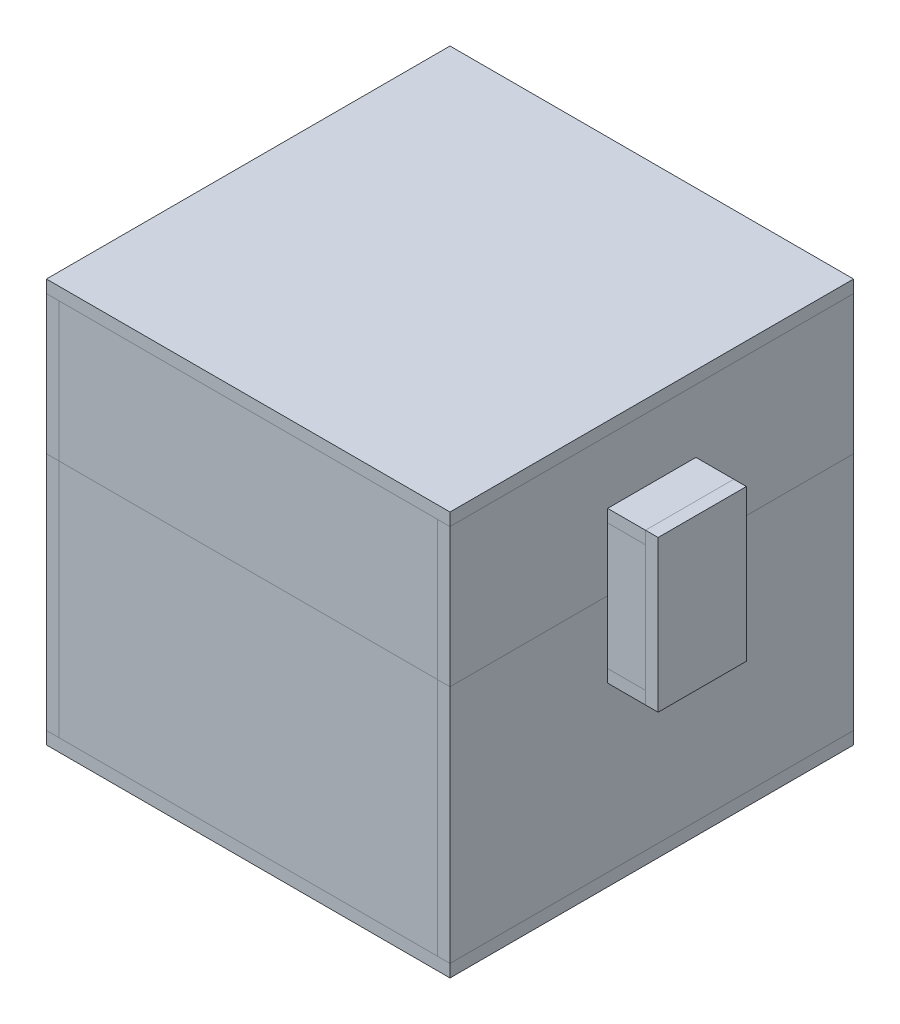
SolidWorks part; units mm, degrees
ref_plane "Front Plane" through (0, 0, 0) normal (0, 0, 1) x (1, 0, 0)
ref_plane "Top Plane" through (0, 0, 0) normal (0, 1, 0) x (1, 0, 0)
ref_plane "Right Plane" through (0, 0, 0) normal (1, 0, 0) x (0, 0, -1)
sketch "Sketch1" plane through (0, 0, 0) normal (0, 1, 0) x (1, 0, 0)
  line L1 (-101.6, -101.6) -> (101.6, -101.6)
  line L2 (-101.6, -101.6) -> (-101.6, 101.6)
  line L3 (-101.6, 101.6) -> (101.6, 101.6)
  line L4 (101.6, -101.6) -> (101.6, 101.6)
  line L5 (-101.6, -101.6) -> (101.6, 101.6) construction
  line L6 (-101.6, 101.6) -> (101.6, -101.6) construction
  point P0 (0, 0)
  dimension "D1" = 203.2
extrude "Boss-Extrude1" add sketch "Sketch1" along normal blind 127
sketch "Sketch2" plane through (0, 127, 0) normal (0, 1, 0) x (1, 0, 0)
  line L20 (95.25, -95.25) -> (95.25, 95.25)
  line L21 (95.25, 95.25) -> (-95.25, 95.25)
  line L22 (-95.25, 95.25) -> (-95.25, -95.25)
  line L23 (-95.25, -95.25) -> (95.25, -95.25)
  line L24 (95.25, -95.25) -> (95.25, 95.25)
  line L25 (95.25, 95.25) -> (-95.25, 95.25)
  line L26 (-95.25, 95.25) -> (-95.25, -95.25)
  line L27 (-95.25, -95.25) -> (95.25, -95.25)
  dimension "D1" = 6.35
extrude "Cut-Extrude1" cut sketch "Sketch2" against normal blind 120.65
sketch "Sketch3" plane through (0, 127, 0) normal (0, 1, 0) x (1, 0, 0)
  line L0 (-101.6, -101.6) -> (101.6, -101.6) construction
  line L1 (101.6, -101.6) -> (101.6, 101.6) construction
  line L2 (-101.6, 101.6) -> (-101.6, -101.6) construction
  line L3 (101.6, 101.6) -> (-101.6, 101.6) construction
  line L4 (-101.6, -101.6) -> (101.6, -101.6)
  line L5 (101.6, -101.6) -> (101.6, 101.6)
  line L6 (-101.6, 101.6) -> (-101.6, -101.6)
  line L7 (101.6, 101.6) -> (-101.6, 101.6)
extrude "Boss-Extrude2" add sketch "Sketch3" along normal blind 76.2 separate body
ref_plane "Plane1" through (-101.6, 127, 101.6) normal (1, 0, 0) x (0, 0, -1)
sketch "Sketch5" plane through (0, 203.2, 0) normal (0, 1, 0) x (1, 0, 0)
  line L8 (-95.25, 95.25) -> (-95.25, -95.25)
  line L9 (-95.25, -95.25) -> (95.25, -95.25)
  line L10 (95.25, -95.25) -> (95.25, 95.25)
  line L11 (95.25, 95.25) -> (-95.25, 95.25)
  line L12 (-95.25, 95.25) -> (-95.25, -95.25)
  line L13 (-95.25, -95.25) -> (95.25, -95.25)
  line L14 (95.25, -95.25) -> (95.25, 95.25)
  line L15 (95.25, 95.25) -> (-95.25, 95.25)
  dimension "D1" = 6.35
extrude "Cut-Extrude2" cut sketch "Sketch5" against normal blind 69.85 from offset 6.35 offset against normal yes
sketch "Sketch6" plane through (0, 0, 0) normal (1, 0, 0) x (0, 0, -1)
  line L0 (-101.6, 127) -> (101.6, 127) construction
  line L1 (-22.225, 88.9) -> (22.225, 88.9)
  line L2 (-22.225, 88.9) -> (-22.225, 165.1)
  line L3 (-22.225, 165.1) -> (22.225, 165.1)
  line L4 (22.225, 88.9) -> (22.225, 165.1)
  line L5 (-22.225, 88.9) -> (22.225, 165.1) construction
  line L6 (-22.225, 165.1) -> (22.225, 88.9) construction
  point P0 (0, 127)
  dimension "D1" = 44.45
  dimension "D2" = 76.2
extrude "Boss-Extrude3" add sketch "Sketch6" along normal blind 25.4 from surface separate body starting at face at (101.6, 165.1, 0)
sketch "Sketch7" plane through (-101.6, 0, 0) normal (-1, 0, 0) x (0, 0, 1)
  line L0 (-76.2, 140) -> (-49.7, 140) construction
  line L1 (-101.6, 127) -> (101.6, 127) construction
  line L2 (-101.6, 203.2) -> (-101.6, 127) construction
  line L3 (0, -111.76) -> (0, 111.76) construction
  circle A0 centre (-76.2, 140) radius 2.5
  circle A1 centre (-49.7, 140) radius 2.5
  circle A2 centre (49.7, 140) radius 2.5
  circle A3 centre (76.2, 140) radius 2.5
  dimension "D2" = 5
  dimension "D1" = 26.5
  dimension "D3" = 13
  dimension "D4" = 25.4
extrude "Cut-Extrude3" cut sketch "Sketch7" against normal up to next (6.35 mm away)
mirror "Mirror4" about plane through (0, 127, 0) normal (0, -1, 0) of "Cut-Extrude3"
sketch "Sketch9" plane through (101.6, 0, 0) normal (-1, 0, 0) x (0, 0, 1)
  line L8 (-15.875, 158.75) -> (-15.875, 95.25)
  line L9 (-15.875, 95.25) -> (15.875, 95.25)
  line L10 (15.875, 95.25) -> (15.875, 158.75)
  line L11 (15.875, 158.75) -> (-15.875, 158.75)
  line L12 (-15.875, 158.75) -> (-15.875, 95.25)
  line L13 (-15.875, 95.25) -> (15.875, 95.25)
  line L14 (15.875, 95.25) -> (15.875, 158.75)
  line L15 (15.875, 158.75) -> (-15.875, 158.75)
  dimension "D1" = 6.35
extrude "Cut-Extrude4" cut sketch "Sketch9" against normal blind 19.05 contours L12 L13 L14 L15
sketch "Sketch10" plane through (120.65, 0, 0) normal (-1, 0, 0) x (0, 0, 1)
  line L4 (15.875, 158.75) -> (-15.875, 158.75)
  line L5 (-15.875, 158.75) -> (-15.875, 95.25)
  line L6 (-15.875, 95.25) -> (15.875, 95.25)
  line L7 (15.875, 95.25) -> (15.875, 158.75)
  line L8 (15.875, 158.75) -> (-15.875, 158.75)
  line L9 (-15.875, 158.75) -> (-15.875, 95.25)
  line L10 (-15.875, 95.25) -> (15.875, 95.25)
  line L11 (15.875, 95.25) -> (15.875, 158.75)
  dimension "D1" = 0
extrude "Boss-Extrude4" add sketch "Sketch10" along normal blind 19.05 separate body
sketch "Sketch12" plane through (101.6, 0, 0) normal (-1, 0, 0) x (0, 0, 1)
  line L0 (0, -111.76) -> (0, 111.76) construction
  line L1 (-9.5, 101.6) -> (9.5, 101.6)
  line L2 (-9.5, 101.6) -> (-9.5, 120.6)
  line L3 (-9.5, 120.6) -> (9.5, 120.6)
  line L4 (9.5, 101.6) -> (9.5, 120.6)
  line L5 (-9.5, 101.6) -> (9.5, 120.6) construction
  line L6 (-9.5, 120.6) -> (9.5, 101.6) construction
  line L7 (-15.875, 95.25) -> (15.875, 95.25) construction
  point P0 (0, 111.1)
  dimension "D1" = 19
  dimension "D2" = 6.35
extrude "Cut-Extrude5" cut sketch "Sketch12" against normal blind 4
sketch "Sketch13" plane through (105.6, 0, 0) normal (-1, 0, 0) x (0, 0, 1)
  line L0 (0, -111.76) -> (0, 111.76) construction
  line L1 (9.5, 101.6) -> (9.5, 120.6) construction
  circle A0 centre (0, 111.1) radius 4.25
  point P4 (0, 0)
  point P7 (9.5, 111.1)
  dimension "D1" = 8.5
extrude "Cut-Extrude6" cut sketch "Sketch13" against normal blind 3 contours A0
sketch "Sketch15" plane through (127, 0, 0) normal (1, 0, 0) x (0, 0, -1)
  line L4 (22.225, 88.9) -> (22.225, 165.1)
  line L5 (22.225, 165.1) -> (-22.225, 165.1)
  line L6 (-22.225, 165.1) -> (-22.225, 88.9)
  line L7 (-22.225, 88.9) -> (22.225, 88.9)
  line L8 (22.225, 88.9) -> (22.225, 165.1)
  line L9 (22.225, 165.1) -> (-22.225, 165.1)
  line L10 (-22.225, 165.1) -> (-22.225, 88.9)
  line L11 (-22.225, 88.9) -> (22.225, 88.9)
  dimension "D1" = 0
extrude "Boss-Extrude5" add sketch "Sketch15" against normal blind 6.35 separate body contours L8 L9 L10 L11
sketch "Sketch16" plane through (0, 165.1, 0) normal (0, 1, 0) x (1, 0, 0)
  line L0 (120.65, 22.225) -> (120.65, -22.225) construction
  line L1 (120.65, 22.225) -> (120.65, -22.225)
  line L4 (101.6, 22.225) -> (101.6, -22.225)
  line L5 (101.6, -22.225) -> (127, -22.225)
  line L6 (127, -22.225) -> (127, 22.225)
  line L7 (127, 22.225) -> (101.6, 22.225)
  line L8 (101.6, 22.225) -> (101.6, -22.225)
  line L9 (101.6, -22.225) -> (120.65, -22.225)
  line L11 (120.65, 22.225) -> (101.6, 22.225)
  dimension "D1" = 0
extrude "Boss-Extrude7" add sketch "Sketch16" against normal blind 6.35 separate body contours L8 L9 L1 L11
sketch "Sketch18" plane through (0, 88.9, 0) normal (0, -1, 0) x (1, 0, 0)
  line L4 (101.6, -22.225) -> (120.65, -22.225)
  line L5 (101.6, 22.225) -> (101.6, -22.225)
  line L6 (120.65, 22.225) -> (101.6, 22.225)
  line L7 (120.65, -22.225) -> (120.65, 22.225)
  line L8 (101.6, -22.225) -> (120.65, -22.225)
  line L9 (101.6, 22.225) -> (101.6, -22.225)
  line L10 (120.65, 22.225) -> (101.6, 22.225)
  line L11 (120.65, -22.225) -> (120.65, 22.225)
  dimension "D1" = 0
extrude "Boss-Extrude8" add sketch "Sketch18" against normal blind 6.35 separate body contours L8 L11 L10 L9
sketch "Sketch19" plane through (0, 0, 15.875) normal (0, 0, 1) x (1, 0, 0)
  line L4 (120.65, 95.25) -> (120.65, 158.75)
  line L5 (120.65, 158.75) -> (101.6, 158.75)
  line L6 (101.6, 158.75) -> (101.6, 95.25)
  line L7 (101.6, 95.25) -> (120.65, 95.25)
  line L8 (120.65, 95.25) -> (120.65, 158.75)
  line L9 (120.65, 158.75) -> (101.6, 158.75)
  line L10 (101.6, 158.75) -> (101.6, 95.25)
  line L11 (101.6, 95.25) -> (120.65, 95.25)
  dimension "D1" = 0
extrude "Boss-Extrude12" add sketch "Sketch19" along normal blind 6.35 separate body contours L8 L9 L10 L11
sketch "Sketch21" plane through (0, 0, -15.875) normal (0, 0, -1) x (-1, 0, 0)
  line L4 (-120.65, 158.75) -> (-120.65, 95.25)
  line L5 (-120.65, 95.25) -> (-101.6, 95.25)
  line L6 (-101.6, 95.25) -> (-101.6, 158.75)
  line L7 (-101.6, 158.75) -> (-120.65, 158.75)
  line L8 (-120.65, 158.75) -> (-120.65, 95.25)
  line L9 (-120.65, 95.25) -> (-101.6, 95.25)
  line L10 (-101.6, 95.25) -> (-101.6, 158.75)
  line L11 (-101.6, 158.75) -> (-120.65, 158.75)
  dimension "D1" = 0
extrude "Boss-Extrude13" add sketch "Sketch21" along normal blind 6.35 separate body
delete or keep bodies "Body-Delete/Keep 1" type delete bodies bodies 108
sketch "Sketch22" plane through (0, 203.2, 0) normal (0, 1, 0) x (1, 0, 0)
  line L4 (-101.6, 101.6) -> (-101.6, -101.6)
  line L5 (-101.6, -101.6) -> (101.6, -101.6)
  line L6 (101.6, -101.6) -> (101.6, 101.6)
  line L7 (101.6, 101.6) -> (-101.6, 101.6)
  line L8 (-101.6, 101.6) -> (-101.6, -101.6)
  line L9 (-101.6, -101.6) -> (101.6, -101.6)
  line L10 (101.6, -101.6) -> (101.6, 101.6)
  line L11 (101.6, 101.6) -> (-101.6, 101.6)
  dimension "D1" = 0
extrude "Boss-Extrude14" add sketch "Sketch22" against normal blind 6.35 separate body
sketch "Sketch23" plane through (101.6, 0, 0) normal (1, 0, 0) x (0, 0, -1)
  line L0 (101.6, 196.85) -> (-101.6, 196.85)
  line L12 (-101.6, 127) -> (101.6, 127)
  line L13 (101.6, 127) -> (101.6, 203.2)
  line L14 (101.6, 203.2) -> (-101.6, 203.2)
  line L15 (-101.6, 203.2) -> (-101.6, 127)
  line L16 (-101.6, 127) -> (101.6, 127)
  line L17 (101.6, 127) -> (101.6, 196.85)
  line L19 (-101.6, 196.85) -> (-101.6, 127)
  dimension "D1" = 0
extrude "Boss-Extrude16" add sketch "Sketch23" against normal blind 6.35 separate body contours L16 L17 L0 L19
sketch "Sketch24" plane through (-101.6, 0, 0) normal (-1, 0, 0) x (0, 0, 1)
  line L0 (-101.6, 196.85) -> (101.6, 196.85)
  line L4 (-101.6, 127) -> (101.6, 127)
  line L5 (101.6, 127) -> (101.6, 203.2)
  line L6 (101.6, 203.2) -> (-101.6, 203.2)
  line L7 (-101.6, 203.2) -> (-101.6, 127)
  line L8 (-101.6, 127) -> (101.6, 127)
  line L9 (101.6, 127) -> (101.6, 196.85)
  line L11 (-101.6, 196.85) -> (-101.6, 127)
  circle A0 centre (76.2, 140) radius 2.5 construction
  circle A1 centre (49.7, 140) radius 2.5 construction
  circle A2 centre (-49.7, 140) radius 2.5 construction
  circle A3 centre (-76.2, 140) radius 2.5 construction
  circle A4 centre (76.2, 140) radius 2.5
  circle A5 centre (49.7, 140) radius 2.5
  circle A6 centre (-49.7, 140) radius 2.5
  circle A7 centre (-76.2, 140) radius 2.5
  dimension "D1" = 0
extrude "Boss-Extrude17" add sketch "Sketch24" against normal blind 6.35 separate body
sketch "Sketch25" plane through (0, 0, 101.6) normal (0, 0, 1) x (1, 0, 0)
  line L0 (-101.6, 127) -> (101.6, 127) construction
  line L1 (-95.25, 127) -> (-95.25, 196.85) construction
  line L2 (95.25, 196.85) -> (95.25, 127) construction
  line L3 (-101.6, 196.85) -> (101.6, 196.85) construction
  line L4 (-95.25, 127) -> (95.25, 127)
  line L5 (-95.25, 127) -> (-95.25, 196.85)
  line L6 (95.25, 196.85) -> (95.25, 127)
  line L7 (-95.25, 196.85) -> (95.25, 196.85)
extrude "Boss-Extrude18" add sketch "Sketch25" against normal blind 6.35 separate body
sketch "Sketch26" plane through (0, 0, -101.6) normal (0, 0, -1) x (-1, 0, 0)
  line L4 (95.25, 127) -> (95.25, 196.85)
  line L5 (-95.25, 127) -> (95.25, 127)
  line L6 (-95.25, 196.85) -> (-95.25, 127)
  line L7 (95.25, 196.85) -> (-95.25, 196.85)
  line L8 (95.25, 127) -> (95.25, 196.85)
  line L9 (-95.25, 127) -> (95.25, 127)
  line L10 (-95.25, 196.85) -> (-95.25, 127)
  line L11 (95.25, 196.85) -> (-95.25, 196.85)
  dimension "D1" = 0
extrude "Boss-Extrude19" add sketch "Sketch26" against normal blind 6.35 separate body contours L8 L11 L10 L9
delete or keep bodies "Body-Delete/Keep 2" type delete bodies bodies 106
sketch "Sketch27" plane through (0, 0, 0) normal (0, -1, 0) x (1, 0, 0)
  line L4 (101.6, -101.6) -> (101.6, 101.6)
  line L5 (101.6, 101.6) -> (-101.6, 101.6)
  line L6 (-101.6, 101.6) -> (-101.6, -101.6)
  line L7 (-101.6, -101.6) -> (101.6, -101.6)
  line L8 (101.6, -101.6) -> (101.6, 101.6)
  line L9 (101.6, 101.6) -> (-101.6, 101.6)
  line L10 (-101.6, 101.6) -> (-101.6, -101.6)
  line L11 (-101.6, -101.6) -> (101.6, -101.6)
  dimension "D1" = 0
extrude "Boss-Extrude20" add sketch "Sketch27" against normal blind 6.35 separate body
sketch "Sketch28" plane through (101.6, 0, 0) normal (1, 0, 0) x (0, 0, -1)
  line L0 (-101.6, 6.35) -> (101.6, 6.35)
  line L4 (-101.6, 0) -> (101.6, 0)
  line L5 (101.6, 0) -> (101.6, 127)
  line L6 (101.6, 127) -> (-101.6, 127)
  line L7 (-101.6, 127) -> (-101.6, 0)
  line L9 (101.6, 6.35) -> (101.6, 127)
  line L10 (101.6, 127) -> (-101.6, 127)
  line L11 (-101.6, 127) -> (-101.6, 6.35)
  dimension "D1" = 0
extrude "Boss-Extrude21" add sketch "Sketch28" against normal blind 6.35 separate body
sketch "Sketch29" plane through (-101.6, 0, 0) normal (-1, 0, 0) x (0, 0, 1)
  line L4 (101.6, 6.35) -> (101.6, 127)
  line L5 (101.6, 127) -> (-101.6, 127)
  line L6 (-101.6, 127) -> (-101.6, 6.35)
  line L7 (-101.6, 6.35) -> (101.6, 6.35)
  line L8 (101.6, 6.35) -> (101.6, 127)
  line L9 (101.6, 127) -> (-101.6, 127)
  line L10 (-101.6, 127) -> (-101.6, 6.35)
  line L11 (-101.6, 6.35) -> (101.6, 6.35)
  circle A0 centre (76.2, 114) radius 2.5 construction
  circle A1 centre (49.7, 114) radius 2.5 construction
  circle A2 centre (-49.7, 114) radius 2.5 construction
  circle A3 centre (-76.2, 114) radius 2.5 construction
  circle A4 centre (76.2, 114) radius 2.5
  circle A5 centre (49.7, 114) radius 2.5
  circle A6 centre (-49.7, 114) radius 2.5
  circle A7 centre (-76.2, 114) radius 2.5
  dimension "D1" = 0
extrude "Boss-Extrude22" add sketch "Sketch29" against normal blind 6.35 separate body
sketch "Sketch30" plane through (0, 0, 101.6) normal (0, 0, 1) x (1, 0, 0)
  line L0 (101.6, 6.35) -> (-101.6, 6.35) construction
  line L1 (95.25, 127) -> (95.25, 6.35) construction
  line L2 (-95.25, 127) -> (95.25, 127) construction
  line L3 (-95.25, 6.35) -> (-95.25, 127) construction
  line L4 (95.25, 6.35) -> (-95.25, 6.35)
  line L5 (95.25, 127) -> (95.25, 6.35)
  line L6 (-95.25, 127) -> (95.25, 127)
  line L7 (-95.25, 6.35) -> (-95.25, 127)
extrude "Boss-Extrude23" add sketch "Sketch30" against normal blind 6.35 separate body
sketch "Sketch31" plane through (0, 0, -101.6) normal (0, 0, -1) x (-1, 0, 0)
  line L4 (95.25, 127) -> (-95.25, 127)
  line L5 (95.25, 6.35) -> (95.25, 127)
  line L6 (-95.25, 6.35) -> (95.25, 6.35)
  line L7 (-95.25, 127) -> (-95.25, 6.35)
  line L8 (95.25, 127) -> (-95.25, 127)
  line L9 (95.25, 6.35) -> (95.25, 127)
  line L10 (-95.25, 6.35) -> (95.25, 6.35)
  line L11 (-95.25, 127) -> (-95.25, 6.35)
  dimension "D1" = 0
extrude "Boss-Extrude24" add sketch "Sketch31" against normal blind 6.35 separate body
delete or keep bodies "Body-Delete/Keep 3" type delete bodies bodies 107
